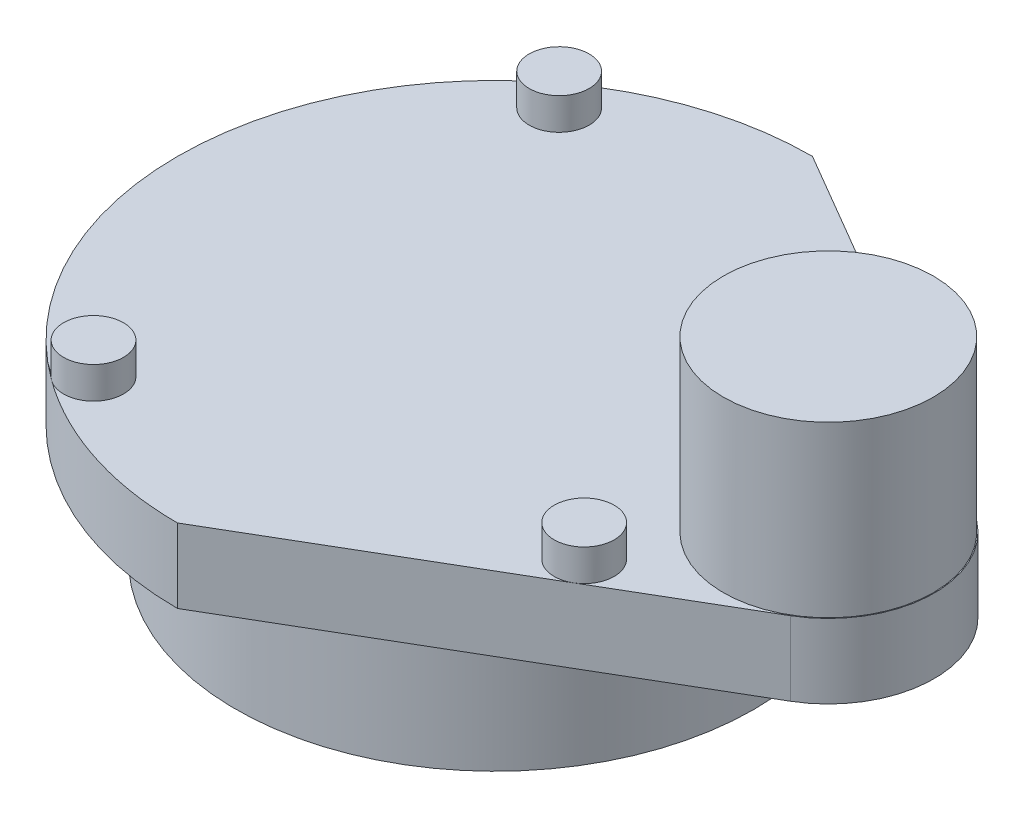
SolidWorks part; units mm, degrees
ref_plane "Front Plane" through (0, 0, 0) normal (0, 0, 1) x (1, 0, 0)
ref_plane "Top Plane" through (0, 0, 0) normal (0, 1, 0) x (1, 0, 0)
ref_plane "Right Plane" through (0, 0, 0) normal (1, 0, 0) x (0, 0, -1)
ref_plane "RIDGE TOP" through (0, -15.875, 0) normal (0, -1, 0) x (-1, 0, 0)
ref_plane "STANDOFF BOTTOM" through (0, 0, 0) normal (0, -1, 0) x (-1, 0, 0)
sketch "Sketch1" plane through (0, 0, 0) normal (0, 1, 0) x (1, 0, 0)
  circle A0 centre (0, 0) radius 38.8937
  dimension "D1" = 77.7875
extrude "Boss-Extrude1" add sketch "Sketch1" against normal blind 17.4625 from surface starting at plane "RIDGE TOP"
sketch "Sketch2" plane through (0, 0, 0) normal (0, -1, 0) x (-1, 0, 0)
  line L0 (0, 0) -> (-65.8812, 0) construction
  line L1 (0, 0) -> (48.4188, 0) construction
  line L2 (0, 47.625) -> (0, -47.625) construction
  line L3 (-58.0186, 13.7047) -> (0, 47.625)
  line L4 (-58.0186, -13.7047) -> (0, -47.625)
  circle A0 centre (0, 0) radius 38.8937 construction
  arc A1 (0, 47.625) -> (0, -47.625) centre (0, 0) cw
  circle A2 centre (-50.0062, 0) radius 7.1437 construction
  circle A3 centre (-50.0062, 0) radius 15.875 construction
  arc A4 (-58.0186, -13.7047) -> (-58.0186, 13.7047) centre (-50.0062, 0) cw
  point P6 (-38.8937, 0)
  point P9 (0, 0)
  point P11 (-50.0062, 0)
  dimension "D5" = 14.2875
  dimension "D1" = 114.3
  dimension "D2" = 26.9875
  dimension "D3" = 95.25
  dimension "D4" = 15.875
extrude "Boss-Extrude2" add sketch "Sketch2" against normal blind 11.1125 from surface starting at plane "RIDGE TOP"
ref_axis "Axis1" through (50.0062, -4.7625, 0) along (0, -1, 0)
sketch "Sketch3" plane through (0, 0, 0) normal (0, -1, 0) x (-1, 0, 0)
  line L0 (25.2984, 34.925) -> (25.2984, -34.925) construction
  line L1 (25.2984, 0) -> (0, 0) construction
  line L2 (-35.208, 21.8281) -> (-35.208, -21.8281) construction
  line L3 (-35.208, 0) -> (0, 0) construction
  line L4 (-58.0186, 13.7047) -> (0, 47.625) construction
  circle A0 centre (-35.208, 21.8281) radius 4.5
  circle A1 centre (-35.208, -21.8281) radius 4.5
  circle A2 centre (25.2984, -34.925) radius 4.5
  circle A3 centre (25.2984, 34.925) radius 4.5
  arc A4 (0, -47.625) -> (0, 47.625) centre (0, 0) ccw construction
  point P8 (25.2984, 0)
  point P12 (-35.208, 0)
  dimension "D3" = 9
  dimension "D1" = 69.85
  dimension "D2" = 43.6562
extrude "Boss-Extrude3" add sketch "Sketch3" along normal up to next
sketch "Sketch4" plane through (0, -4.7625, 0) normal (0, 1, 0) x (1, 0, 0)
  circle A0 centre (50.0062, 0) radius 15.748
  arc A1 (58.0186, -13.7047) -> (58.0186, 13.7047) centre (50.0062, 0) ccw construction
  arc A2 (58.0186, -13.7047) -> (58.0186, 13.7047) centre (50.0062, 0) ccw construction
  dimension "D1" = 31.496
extrude "Boss-Extrude4" add sketch "Sketch4" along normal blind 25.4
equation "\"D1@Boss-Extrude1\"=0.75-0.0625"
